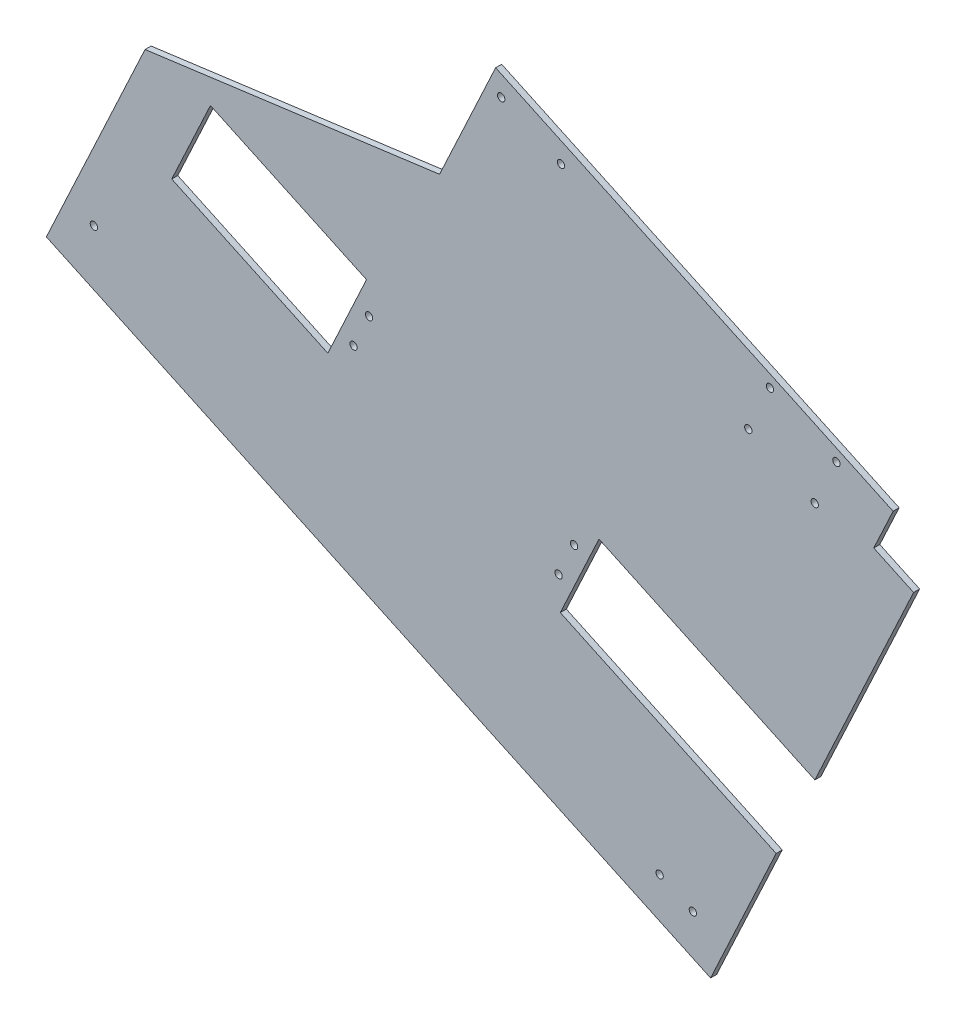
SolidWorks part; units mm, degrees
material "Balsa"
ref_plane "Front Plane" through (0, 0, 0) normal (0, 0, 1) x (1, 0, 0)
ref_plane "Top Plane" through (0, 0, 0) normal (0, 1, 0) x (1, 0, 0)
ref_plane "Right Plane" through (0, 0, 0) normal (1, 0, 0) x (0, 0, -1)
sketch "Sketch1" plane through (0, 0, 0) normal (0, 0, 1) x (1, 0, 0)
  line L0 (-278.5096, -37.3286) -> (-117.7638, -15.9332)
  line L1 (-117.7638, -15.9332) -> (-87.1479, 49.7228)
  line L2 (-87.1479, 49.7228) -> (129.7831, -51.4338)
  line L3 (129.7831, -51.4338) -> (119.2177, -74.0915)
  line L4 (119.2177, -74.0915) -> (140.969, -84.2344)
  line L5 (140.969, -84.2344) -> (30.1585, -321.8683)
  line L6 (30.1585, -321.8683) -> (-332.3646, -152.8209)
  line L7 (-332.3646, -152.8209) -> (-278.5096, -37.3286)
  line L9 (-332.3646, -152.8209) -> (-261.0998, 0.0069) construction
  line L10 (30.1585, -321.8683) -> (-332.3646, -152.8209) construction
  line L11 (140.969, -84.2344) -> (30.1585, -321.8683) construction
  line L12 (-189.2372, 97.3278) -> (129.7831, -51.4338) construction
  line L13 (119.2177, -74.0915) -> (140.969, -84.2344) construction
  line L14 (129.7831, -51.4338) -> (119.2177, -74.0915) construction
  line L15 (-110.3324, 0.0035) -> (-87.1479, 49.7228) construction
  line L17 (-273.6131, -36.6769) -> (-75.3615, -10.2894) construction
  circle A0 centre (87.0035, -69.0002) radius 2
  circle A1 centre (98.8369, -43.6236) radius 2
  circle A2 centre (62.5845, -26.7189) radius 2
  circle A3 centre (50.7512, -52.0955) radius 2
  circle A4 centre (2.3586, -286.8374) radius 2
  circle A5 centre (-306.4229, -134.5749) radius 2
  circle A6 centre (20.4847, -295.2897) radius 2
  circle A7 centre (2.3586, -286.8374) radius 2 construction
  circle A8 centre (20.4847, -295.2897) radius 2 construction
  dimension "D1" = 4
  dimension "D2" = 4
  dimension "D3" = 4
  dimension "D4" = 4
  dimension "D7" = 4
  dimension "D5" = 27.5
  dimension "D6" = 15.8
extrude "Boss-Extrude1" add sketch "Sketch1" along normal up to surface (3.3 mm away)
sketch "Sketch2" plane through (0, 0, 0) normal (0, 0, -1) x (-1, 0, 0)
  line L0 (87.1479, 49.7228) -> (117.7638, -15.9332) construction
  line L1 (-129.7831, -51.4338) -> (87.1479, 49.7228) construction
  circle A0 centre (51.4966, 22.0645) radius 2
  circle A1 centre (84.1237, 37.2788) radius 2
  dimension "D1" = 4
  dimension "D2" = 4
  dimension "D3" = 8
  dimension "D4" = 36
  dimension "D5" = 10
  dimension "D6" = 10
extrude "Cut-Extrude1" cut sketch "Sketch2" against normal through all
sketch "Sketch5" plane through (0, 0, 3.3) normal (0, 0, 1) x (1, 0, 0)
  line L0 (65.9543, -245.104) -> (-51.8657, -190.1636)
  line L1 (140.969, -84.2344) -> (30.1585, -321.8683) construction
  line L2 (-51.8657, -190.1636) -> (-30.7348, -144.8482)
  line L3 (-30.7348, -144.8482) -> (87.0852, -199.7886)
  line L4 (87.0852, -199.7886) -> (65.9543, -245.104)
  line L5 (119.2177, -74.0915) -> (140.969, -84.2344) construction
  dimension "D1" = 130
  dimension "D2" = 127.5
  dimension "D3" = 50
extrude "Cut-Extrude2" cut sketch "Sketch5" against normal blind 10
sketch "Sketch6" plane through (0, 0, 3.3) normal (0, 0, 1) x (1, 0, 0)
  line L0 (-178.7488, -130.9971) -> (-157.6179, -85.6817)
  line L1 (-157.6179, -85.6817) -> (-242.8108, -45.9555)
  line L2 (-242.8108, -45.9555) -> (-263.9417, -91.2709)
  line L3 (-263.9417, -91.2709) -> (-178.7488, -130.9971)
  line L5 (87.0852, -199.7886) -> (-30.7348, -144.8482) construction
  line L6 (-51.8657, -190.1636) -> (65.9543, -245.104) construction
  line L7 (-332.3646, -152.8209) -> (-278.5096, -37.3286) construction
  line L8 (129.7831, -51.4338) -> (119.2177, -74.0915) construction
  dimension "D1" = 130
  dimension "D2" = 340
extrude "Cut-Extrude3" cut sketch "Sketch6" against normal blind 10
sketch "Sketch7" plane through (0, 0, 3.3) normal (0, 0, 1) x (1, 0, 0)
  circle A0 centre (-52.7985, -172.5711) radius 2
  circle A1 centre (-44.3462, -154.4449) radius 2
  circle A2 centre (-164.6725, -120.4034) radius 2
  circle A3 centre (-156.2202, -102.2772) radius 2
  circle A4 centre (-52.7985, -172.5711) radius 2 construction
  circle A5 centre (-44.3462, -154.4449) radius 2 construction
  circle A6 centre (-164.6725, -120.4034) radius 2 construction
  circle A7 centre (-156.2202, -102.2772) radius 2 construction
extrude "Cut-Extrude4" cut sketch "Sketch7" against normal blind 10
